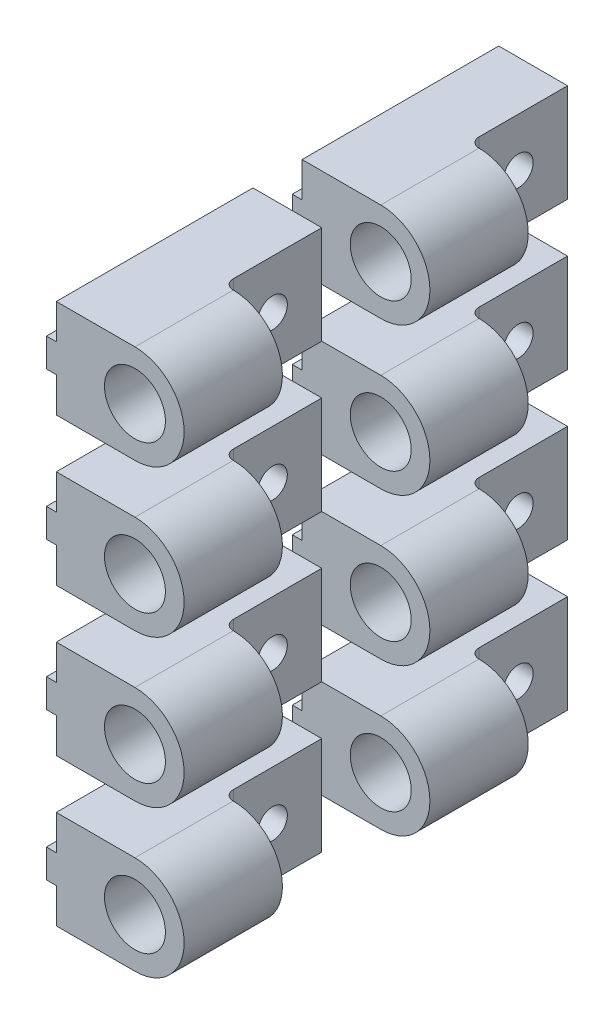
SolidWorks part; units mm, degrees
ref_plane "Front Plane" through (0, 0, 0) normal (0, 0, 1) x (1, 0, 0)
ref_plane "Top Plane" through (0, 0, 0) normal (0, 1, 0) x (1, 0, 0)
ref_plane "Right Plane" through (0, 0, 0) normal (1, 0, 0) x (0, 0, -1)
sketch "Sketch1" plane through (0, 0, 0) normal (0, 0, 1) x (1, 0, 0)
  line L0 (-8, 5) -> (-8, 1.45)
  line L1 (-8, 1.45) -> (-9, 1.45)
  line L2 (-9, 1.45) -> (-9, -1.45)
  line L3 (-9, -1.45) -> (-8, -1.45)
  line L4 (-8, -1.45) -> (-8, -5)
  line L5 (-8, -5) -> (0, -5)
  line L6 (-8, 5) -> (0, 5)
  arc A0 (0, -5) -> (0, 5) centre (0, 0) ccw
  dimension "D1" = 10
  dimension "D2" = 2.9
  dimension "D3" = 1
  dimension "D4" = 8
extrude "Main" add sketch "Sketch1" along normal blind 20
ref_plane "Plane1" through (-1, 0, 0) normal (-1, 0, 0) x (0, 0, 1)
sketch "Sketch2" plane through (0, 0, 20) normal (0, 0, 1) x (1, 0, 0)
  circle A0 centre (0, 0) radius 3.1
  dimension "D1" = 6.2
extrude "ShaftHole" cut sketch "Sketch2" against normal blind 5
sketch "Sketch3" plane through (-1, 0, 0) normal (1, 0, 0) x (0, 0, -1)
  line L0 (-20, 5) -> (0, 5) construction
  line L1 (-10, 5) -> (0, 5)
  line L2 (-10, 5) -> (-10, -5)
  line L3 (-10, -5) -> (0, -5)
  line L4 (0, 5) -> (0, -5)
  line L5 (-20, -5) -> (0, -5) construction
  line L6 (0, -5) -> (0, 5) construction
  dimension "D1" = 10
extrude "MakerBeamRectangularHole" cut sketch "Sketch3" along normal through all
sketch "Sketch4" plane through (-1, 0, 0) normal (1, 0, 0) x (0, 0, -1)
  line L0 (0, -5) -> (0, 5) construction
  circle A0 centre (-5, 0) radius 1.5
  dimension "D1" = 3
  dimension "D2" = 5
extrude "MakerBeamHole" cut sketch "Sketch4" against normal through all
fillet "Fillet1" radius 1 1 edges at (-1, 0, 10)
pattern_linear "LPattern1" count 4 spacing 15 along (0, -1, 0) count 2 spacing 25 along (0, 0, 1) of bodies 104
